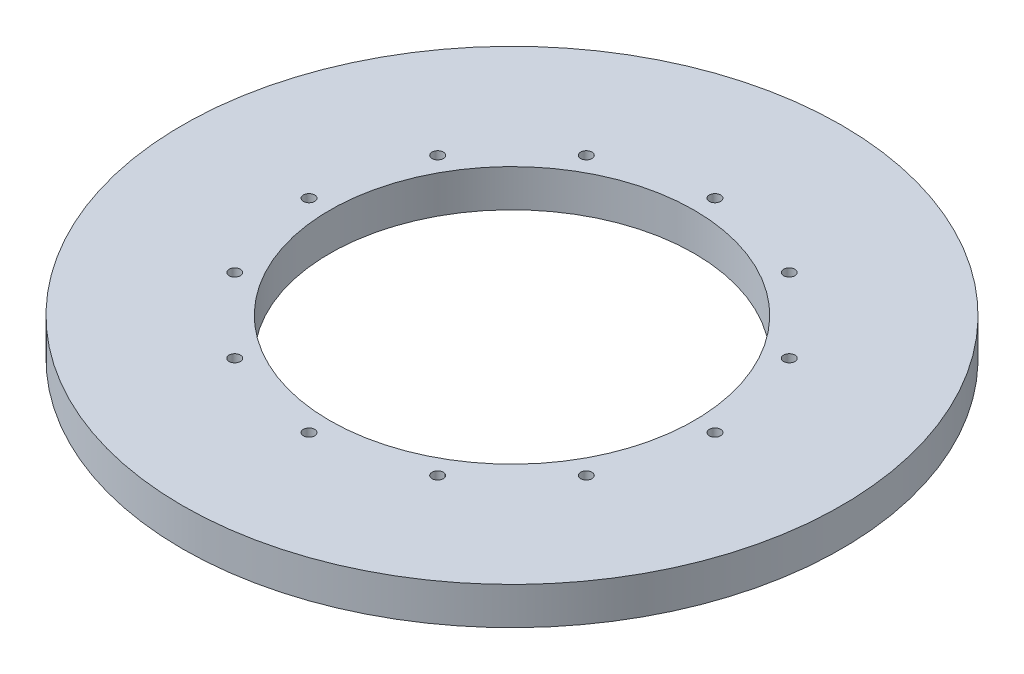
SolidWorks part; units mm, degrees
material "6061-T6 (SS)"
ref_plane "Front Plane" through (0, 0, 0) normal (0, 0, 1) x (1, 0, 0)
ref_plane "Top Plane" through (0, 0, 0) normal (0, 1, 0) x (1, 0, 0)
ref_plane "Right Plane" through (0, 0, 0) normal (1, 0, 0) x (0, 0, -1)
sketch "Sketch1" plane through (0, 0, 0) normal (0, 1, 0) x (1, 0, 0)
  line L5 (0, 0) -> (127.635, 0)
  line L6 (0, 0) -> (0, 127.635)
  line L7 (0, 127.635) -> (127.635, 127.635)
  line L8 (127.635, 0) -> (127.635, 127.635)
  dimension "D1" = 127.635
  dimension "D2" = 127.635
extrude "Boss-Extrude1" add sketch "Sketch1" along normal blind 9.525 contours L5 L8 L7 L6
sketch "Sketch12" plane through (0, 0, 0) normal (0, -1, 0) x (1, 0, 0)
  line L0 (63.8175, 0) -> (63.8175, -127.635) construction
  line L1 (0, 0) -> (127.635, 0) construction
  line L2 (0, -127.635) -> (127.635, -127.635) construction
  line L3 (0, -63.8175) -> (127.635, -63.8175) construction
  line L4 (0, 0) -> (0, -127.635) construction
  line L5 (127.635, 0) -> (127.635, -127.635) construction
  circle A0 centre (63.8175, -63.8175) radius 83.82
  dimension "D1" = 167.64
extrude "Boss-Extrude2" add sketch "Sketch12" against normal up to surface (9.525 mm away) contours A0 up to face at (63.8175, 9.525, -63.8175)
sketch "Sketch13" plane through (0, 0, 0) normal (0, -1, 0) x (-1, 0, 0)
  circle A0 centre (-63.8175, 63.8175) radius 83.82
  circle A1 centre (-63.8175, 63.8175) radius 104.9285
  dimension "D1" = 167.64
extrude "Cut-Extrude4" cut sketch "Sketch13" against normal up to surface (9.525 mm away) contours A1 | A0 up to face at (63.8175, 9.525, -63.8175)
sketch "Sketch5" plane through (0, 9.525, 0) normal (0, 1, 0) x (1, 0, 0)
  circle A0 centre (63.8175, 63.8175) radius 46.355
  circle A1 centre (63.8175, 63.8175) radius 83.82 construction
  dimension "D1" = 92.71
extrude "Cut-Extrude1" cut sketch "Sketch5" against normal blind 9.525
sketch "Sketch11" plane through (0, 9.525, 0) normal (0, 1, 0) x (1, 0, 0)
  line L0 (63.8175, 63.8175) -> (63.8175, 115.443) construction
  circle A0 centre (63.8175, 115.443) radius 1.4351
  dimension "D2" = 2.8702
  dimension "D1" = 51.6255
extrude "Cut-Extrude3" cut sketch "Sketch11" against normal through all contours A0
pattern_circular "CirPattern1" count 12 over 360 about axis through (63.8175, 9.525, -63.8175) along (0, 1, 0) of "Cut-Extrude3"
